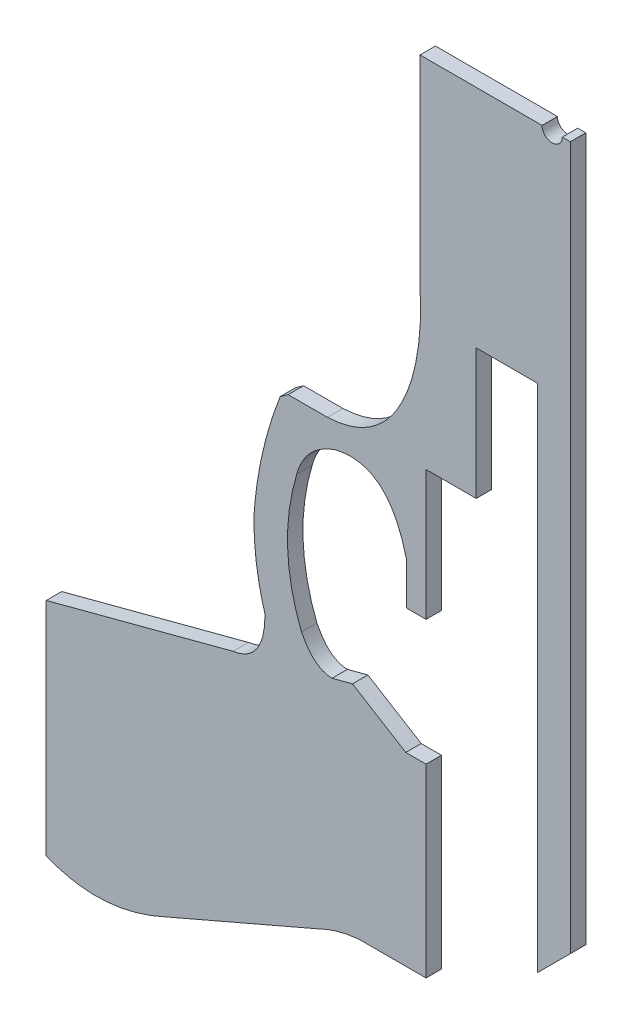
SolidWorks part; units mm, degrees
ref_plane "Front Plane" through (0, 0, 0) normal (0, 0, 1) x (1, 0, 0)
ref_plane "Top Plane" through (0, 0, 0) normal (0, 1, 0) x (1, 0, 0)
ref_plane "Right Plane" through (0, 0, 0) normal (1, 0, 0) x (0, 0, -1)
sketch "Sketch1" plane through (0, 0, 0) normal (0, 0, 1) x (1, 0, 0)
  line L0 (275.5001, 1169.5) -> (1377.5001, 1169.5) construction
  line L1 (1223.2508, 302.0809) -> (1223.2508, 662.4431)
  line L2 (1504.0267, 1851.6657) -> (1504.0267, 483.4465)
  line L3 (1504.0267, 483.4465) -> (1440.1807, 419.6005)
  line L10 (1223.2508, 302.0809) -> (1092.9409, 302.0809)
  line L11 (1015.9055, 281.0273) -> (719.1393, 152.8095)
  line L12 (484.2038, 138.3379) -> (484.2038, 568.7825)
  line L13 (484.2038, 568.7825) -> (865.8528, 669.5981)
  line L14 (1184.9114, 906.3998) -> (1184.9114, 989.604)
  line L17 (1211.4401, 1851.6657) -> (1448.9097, 1851.6657)
  line L18 (1488.3065, 1851.6657) -> (1504.0267, 1851.6657)
  line L19 (1223.2508, 662.4431) -> (1183.8478, 662.4431)
  line L20 (1183.8478, 662.4431) -> (1080.1432, 726.2045)
  line L21 (1440.1807, 419.6005) -> (1440.1807, 1412.6805)
  line L22 (1440.1807, 1412.6805) -> (1320.8738, 1412.6805)
  line L23 (1320.8738, 1412.6805) -> (1320.8738, 1158.9355)
  line L24 (1320.8738, 1158.9355) -> (1223.2508, 1158.9355)
  line L25 (1223.2508, 1158.9355) -> (1223.2508, 906.3998)
  line L26 (1223.2508, 906.3998) -> (1184.9114, 906.3998)
  line L28 (1211.4401, 1851.6657) -> (1211.4401, 1389.4791)
  line L29 (939.4205, 1139.9989) -> (954.92, 1150.948)
  line L30 (954.92, 1150.948) -> (1031.5026, 1150.948)
  line L31 (1040.2748, 715.673) -> (1080.1432, 726.2045)
  arc A0 (1448.9097, 1851.6657) -> (1488.3065, 1851.6657) centre (1468.6081, 1851.6657) ccw
  spline S0 degree 2 poles (1092.9409, 302.0809) (1050.3612, 298.5406) (1013.5706, 279.8599) knots 0 0 0 1 1 1
  spline S1 degree 2 poles (719.1393, 152.8095) (593.119, 93.5306) (484.2038, 138.3379) knots 0 0 0 1 1 1
  spline S4 degree 3 poles (1031.5026, 1150.948) (1184.3344, 1157.0666) (1219.9683, 1335.1337) (1211.4401, 1458.4579) knots 0 0 0 0 1 1 1 1
  spline S5 degree 2 poles (939.4205, 1139.9989) (896.1149, 1029.5) (888.3899, 913.7089) knots 0 0 0 1 1 1
  spline S6 degree 2 poles (888.3899, 913.7089) (887.187, 833.4761) (909.9654, 758.4335) knots 0 0 0 1 1 1
  spline S7 degree 2 poles (909.9654, 758.4335) (909.6629, 673.9311) (847.8627, 664.8458) knots 0 0 0 1 1 1
  spline S8 degree 2 poles (1184.9114, 989.604) (1150.2535, 1129.3685) (1045.7035, 1103.5946) knots 0 0 0 1 1 1
  spline S9 degree 2 poles (1045.7035, 1103.5946) (987.8969, 1083.6042) (971.7427, 1025.6676) knots 0 0 0 1 1 1
  spline S10 degree 2 poles (971.7427, 1025.6676) (931.4355, 890.5008) (980.8663, 763.899) knots 0 0 0 1 1 1
  spline S11 degree 2 poles (980.8663, 763.899) (1005.4417, 715.9345) (1040.2748, 715.673) knots 0 0 0 0.703911 0.703911 0.703911
extrude "Boss-Extrude2" add sketch "Sketch1" along normal blind 30 contours L0 S4 L30 L29 S5 S6 S7 L13 L12 S1 L11 S0 L10 L1 L19 L20 L31 S11 S10 S9 S8 L14 L26 L25 L24 L23 | S4 L0 L23 L22 L21 L3 L2 L18 A0 L17 L28 region at (1197.5892, 1259.3647, 0) region at (868.7139, 514.2928, 0)
